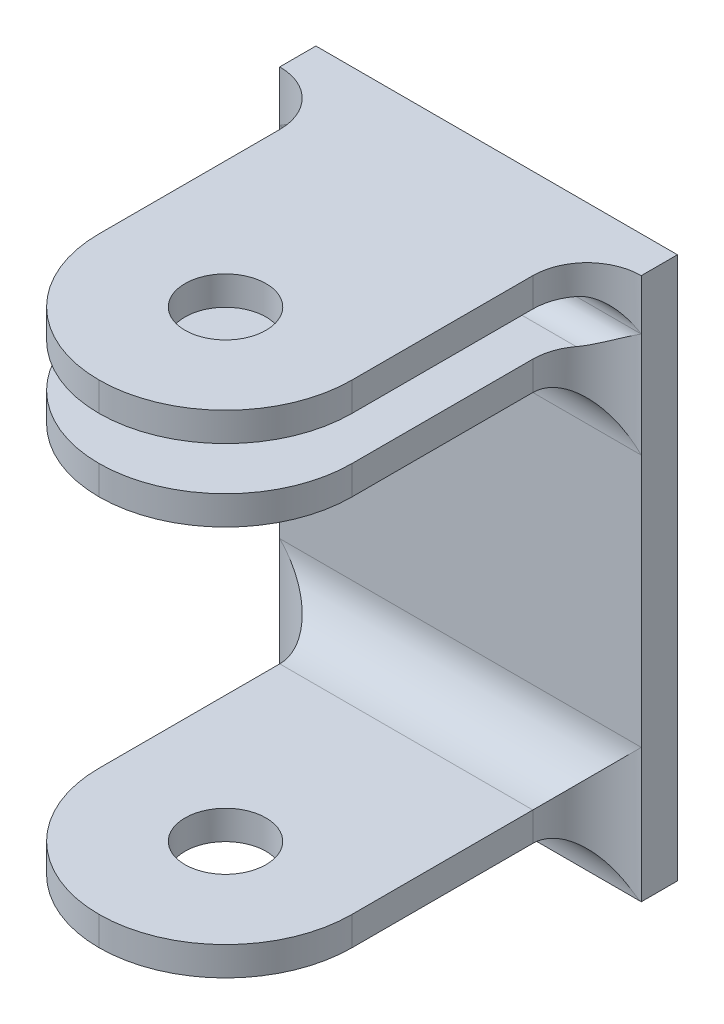
SolidWorks part; units mm, degrees
ref_plane "Plan de face" through (0, 0, 0) normal (1, 0, 0) x (0, 1, 0)
ref_plane "Plan de dessus" through (0, 0, 0) normal (0, 0, 1) x (0, 1, 0)
ref_plane "Plan de droite" through (0, 0, 0) normal (0, 1, 0) x (-1, 0, 0)
sketch "Esquisse1" plane through (0, 0, 0) normal (0, 0, 1) x (0, 1, 0)
  line L1 (0, 0) -> (150, 0)
  line L2 (0, 0) -> (0, 100)
  line L3 (0, 100) -> (150, 100)
  line L4 (150, 0) -> (150, 100)
  dimension "D1" = 150
  dimension "D2" = 100
extrude "Boss.-Extru.1" add sketch "Esquisse1" along normal blind 10
sketch "Esquisse2" plane through (0, 0, 10) normal (0, 0, 1) x (1, 0, 0)
  line L0 (-100, 150) -> (-100, 0) construction
  line L1 (-85, 130) -> (-15, 130)
  line L2 (-85, 130) -> (-85, 122)
  line L3 (-85, 122) -> (-15, 122)
  line L4 (-15, 130) -> (-15, 122)
  line L5 (-85, 150) -> (-15, 150)
  line L6 (0, 0) -> (0, 150) construction
  line L7 (0, 150) -> (-100, 150) construction
  line L8 (-85, 22) -> (-15, 22)
  line L9 (-85, 22) -> (-85, 14)
  line L10 (-85, 14) -> (-15, 14)
  line L11 (-15, 22) -> (-15, 14)
  line L12 (-85, 150) -> (-85, 142)
  line L13 (-85, 142) -> (-15, 142)
  line L14 (-15, 150) -> (-15, 142)
  dimension "D1" = 8
  dimension "D2" = 8
  dimension "D3" = 100
  dimension "D4" = 70
  dimension "D5" = 15
  dimension "D6" = 70
  dimension "D7" = 15
  dimension "D8" = 12
  dimension "D9" = 70
  dimension "D10" = 8
  dimension "D11" = 15
extrude "Boss.-Extru.2" add sketch "Esquisse2" along normal blind 100
fillet "Congé1" radius 35 6 edges at (-85, 126, 110) (-15, 126, 110) (-15, 18, 110) (-85, 18, 110) (-85, 146, 110) (-15, 146, 110)
sketch "Esquisse3" plane through (0, 150, 0) normal (0, 1, 0) x (-1, 0, 0)
  line L0 (0, 10) -> (0, 0) construction
  line L2 (0, 0) -> (100, 0) construction
  circle A0 centre (50, 75) radius 11.2
  dimension "D3" = 22.4
  dimension "D1" = 50
  dimension "D2" = 75
extrude "Enlèv. mat.-Extru.1" cut sketch "Esquisse3" against normal blind 150
fillet "Congé2" radius 15 9 edges at (-15, 18, 10) (-50, 22, 10) (-85, 18, 10) (-50, 14, 10) (-85, 146, 10) (-15, 146, 10) (-15, 126, 10) (-50, 122, 10) (-85, 126, 10)
fillet "Congé3" radius 6 2 edges at (-50, 142, 10) (-50, 130, 10)
